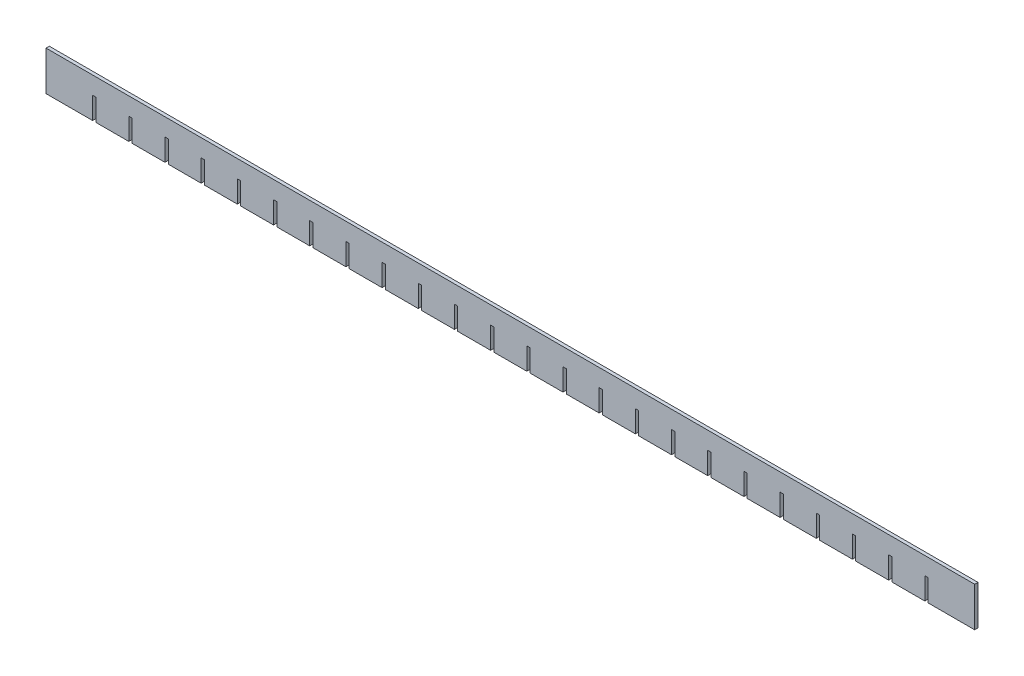
SolidWorks part; units mm, degrees
ref_plane "Ebene vorne" through (0, 0, 0) normal (0, 0, 1) x (1, 0, 0)
ref_plane "Ebene oben" through (0, 0, 0) normal (0, 1, 0) x (1, 0, 0)
ref_plane "Ebene rechts" through (0, 0, 0) normal (1, 0, 0) x (0, 0, -1)
sketch "Sketch1" plane through (0, 0, 0) normal (0, 0, 1) x (1, 0, 0)
  line L1 (-423.5, -18) -> (423.5, -18)
  line L2 (-423.5, -18) -> (-423.5, 18)
  line L3 (-423.5, 18) -> (423.5, 18)
  line L4 (423.5, -18) -> (423.5, 18)
  line L5 (-423.5, -18) -> (423.5, 18) construction
  line L6 (-423.5, 18) -> (423.5, -18) construction
  point P0 (0, 0)
  dimension "D1" = 36
  dimension "D2" = 847
extrude "Boss-Extrude1" add sketch "Sketch1" along normal blind 3
sketch "Sketch2" plane through (0, 0, 3) normal (0, 0, 1) x (1, 0, 0)
  line L6 (-423.5, -18) -> (-381, -18)
  line L7 (-423.5, -18) -> (423.5, -18) construction
  line L8 (-381, -18) -> (-381, 2)
  line L9 (-381, 2) -> (-378, 2)
  line L10 (-378, 2) -> (-378, -18)
  line L11 (-381, -18) -> (-378, -18)
  point P4 (-379.5, -18)
  dimension "D1" = 44
  dimension "D2" = 20
  dimension "D3" = 3
extrude "Cut-Extrude1" cut sketch "Sketch2" against normal through all contours L11 L10 L9 L8
pattern_linear "LPattern1" count 24 spacing 33 along (1, 0, 0) of "Cut-Extrude1"
